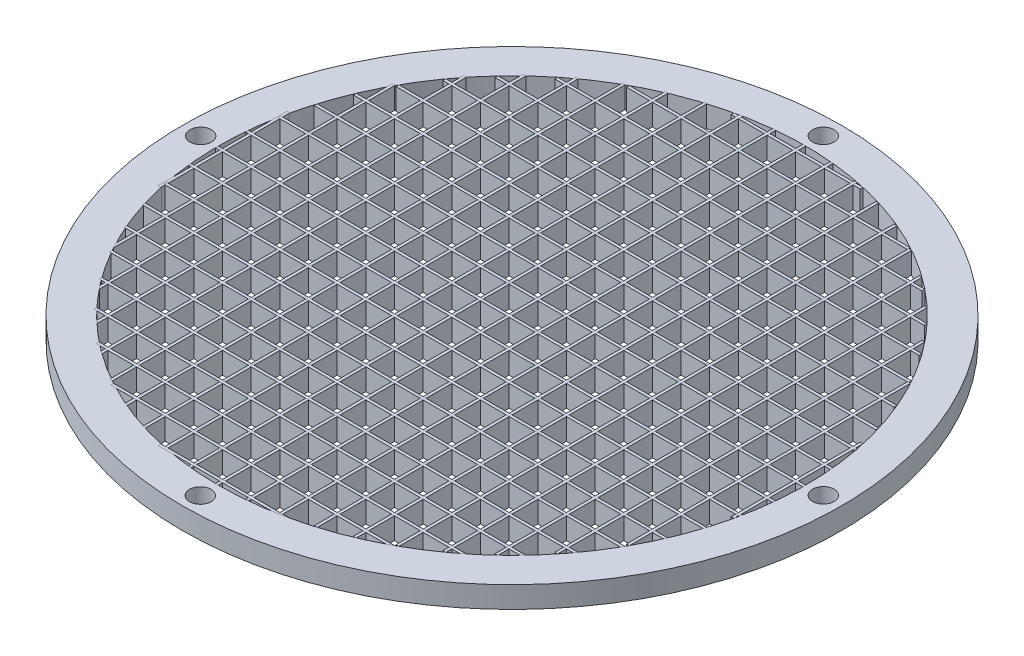
SolidWorks part; units mm, degrees
ref_plane "Front Plane" through (0, 0, 0) normal (0, 0, 1) x (1, 0, 0)
ref_plane "Top Plane" through (0, 0, 0) normal (0, 1, 0) x (1, 0, 0)
ref_plane "Right Plane" through (0, 0, 0) normal (1, 0, 0) x (0, 0, -1)
sketch "Sketch2" plane through (0, 0, 0) normal (0, 1, 0) x (1, 0, 0)
  circle A1 centre (0, 0) radius 41
  circle A2 centre (0, 0) radius 46
  point P208 (0, 0)
extrude "Boss-Extrude2" add sketch "Sketch2" along normal blind 3
sketch "Sketch4" plane through (0, 3, 0) normal (0, 1, 0) x (1, 0, 0)
  line L0 (0, 41) -> (0, -41)
  line L1 (4, 40.8044) -> (4, -40.8044)
  line L2 (8, 40.2119) -> (8, -40.2119)
  line L3 (12, 39.2046) -> (12, -39.2046)
  line L4 (16, 37.7492) -> (16, -37.7492)
  line L5 (20, 35.7911) -> (20, -35.7911)
  line L6 (24, 33.2415) -> (24, -33.2415)
  line L7 (28, 29.95) -> (28, -29.95)
  line L8 (32, 25.632) -> (32, -25.632)
  line L9 (36, 19.6214) -> (36, -19.6214)
  line L10 (40, 9) -> (40, -9)
  line L11 (-41, 0) -> (41, 0)
  line L12 (-4, 40.8044) -> (-4, -40.8044)
  line L13 (-8, 40.2119) -> (-8, -40.2119)
  line L14 (-12, 39.2046) -> (-12, -39.2046)
  line L15 (-16, 37.7492) -> (-16, -37.7492)
  line L16 (-20, 35.7911) -> (-20, -35.7911)
  line L17 (-24, 33.2415) -> (-24, -33.2415)
  line L18 (-28, 29.95) -> (-28, -29.95)
  line L19 (-32, 25.632) -> (-32, -25.632)
  line L20 (-36, 19.6214) -> (-36, -19.6214)
  line L21 (-40, 9) -> (-40, -9)
  line L22 (-40.8042, -4) -> (40.8042, -4)
  line L23 (-44, 41) -> (-44, -41) [skipped]
  line L24 (44, 41) -> (44, -41) [skipped]
  line L25 (-40.2119, -8) -> (40.2119, -8)
  line L26 (-39.2046, -12) -> (39.2046, -12)
  line L27 (-37.7492, -16) -> (37.7492, -16)
  line L28 (-35.7911, -20) -> (35.7911, -20)
  line L29 (-33.2415, -24) -> (33.2415, -24)
  line L30 (-29.95, -28) -> (29.95, -28)
  line L31 (-25.632, -32) -> (25.632, -32)
  line L32 (-19.6214, -36) -> (19.6214, -36)
  line L33 (-9, -40) -> (9, -40)
  line L34 (-9, 40) -> (9, 40)
  line L35 (-19.6214, 36) -> (19.6214, 36)
  line L36 (-25.632, 32) -> (25.632, 32)
  line L37 (-29.95, 28) -> (29.95, 28)
  line L38 (-33.2415, 24) -> (33.2415, 24)
  line L39 (-35.7911, 20) -> (35.7911, 20)
  line L40 (-37.7492, 16) -> (37.7492, 16)
  line L41 (-39.2046, 12) -> (39.2046, 12)
  line L42 (-40.2119, 8) -> (40.2119, 8)
  line L43 (-40.8042, 4) -> (40.8042, 4)
  circle A0 centre (0, 0) radius 41 construction
  point P57 (41, 0)
  point P94 (41.237, 3.3214)
  point P95 (41.2203, 4.9091)
  dimension "D1" = 12
  dimension "D2" = 12
  dimension "D3" = 11
extrude "Extrude-Thin5" add sketch "Sketch4" against normal blind 3 separate body thin thin type one direction wall 0.4
sketch "Sketch5" plane through (0, 0, 0) normal (0, -1, 0) x (1, 0, 0)
  circle A0 centre (0, -43.4524) radius 1.5
  circle A1 centre (-43.4524, 0) radius 1.5
  circle A3 centre (43.4524, 0) radius 1.5
  circle A4 centre (0, 43.4524) radius 1.5 [skipped]
  point P11 (0, 0)
  dimension "D1" = 4
extrude "Cut-Extrude1" cut sketch "Sketch5" against normal blind 3
sketch "Sketch6" plane through (0, 3, 0) normal (0, 1, 0) x (1, 0, 0)
  circle A1 centre (0, -43.5) radius 1.5
  point P0 (0, -43.5)
  point P36 (0, 3)
  dimension "D1" = 43.5
extrude "Cut-Extrude2" cut sketch "Sketch6" against normal through all
